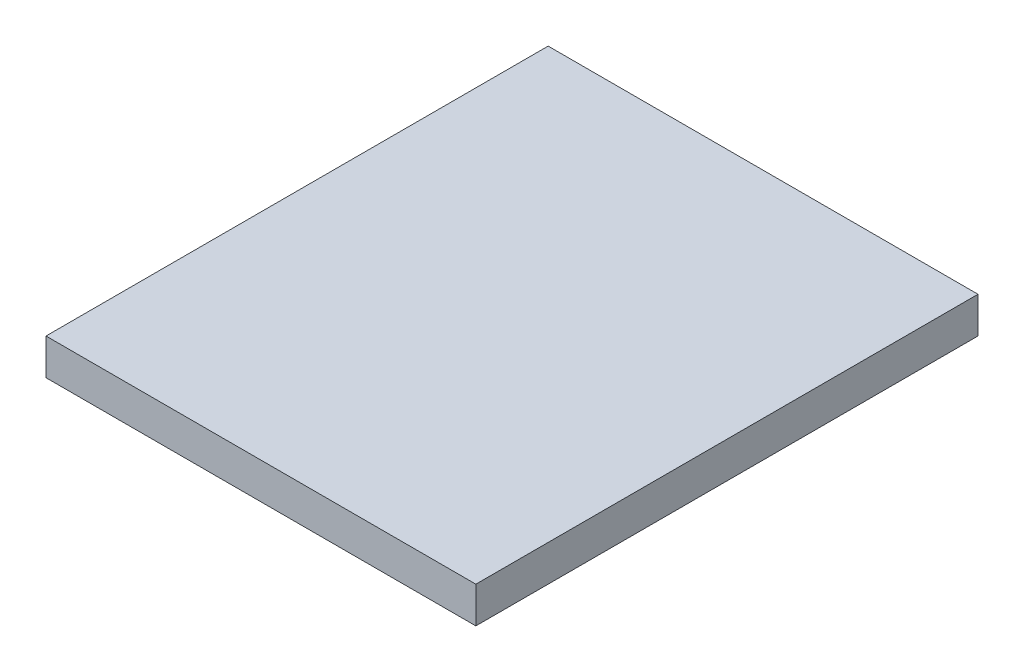
SolidWorks part; units mm, degrees
ref_plane "前视基准面" through (0, 0, 0) normal (0, 0, 1) x (1, 0, 0)
ref_plane "上视基准面" through (0, 0, 0) normal (0, 1, 0) x (1, 0, 0)
ref_plane "右视基准面" through (0, 0, 0) normal (1, 0, 0) x (0, 0, -1)
other "Configuration Table"
sketch "草图1" plane through (0, 0, 0) normal (0, 1, 0) x (1, 0, 0)
  line L1 (-107, -125) -> (107, -125)
  line L2 (-107, -125) -> (-107, 125)
  line L3 (-107, 125) -> (107, 125)
  line L4 (107, -125) -> (107, 125)
  point P4 (-107, 0)
  point P6 (0, 125)
  dimension "D1" = 250
  dimension "D2" = 214
extrude "凸台-拉伸1" add sketch "草图1" along normal blind 18
